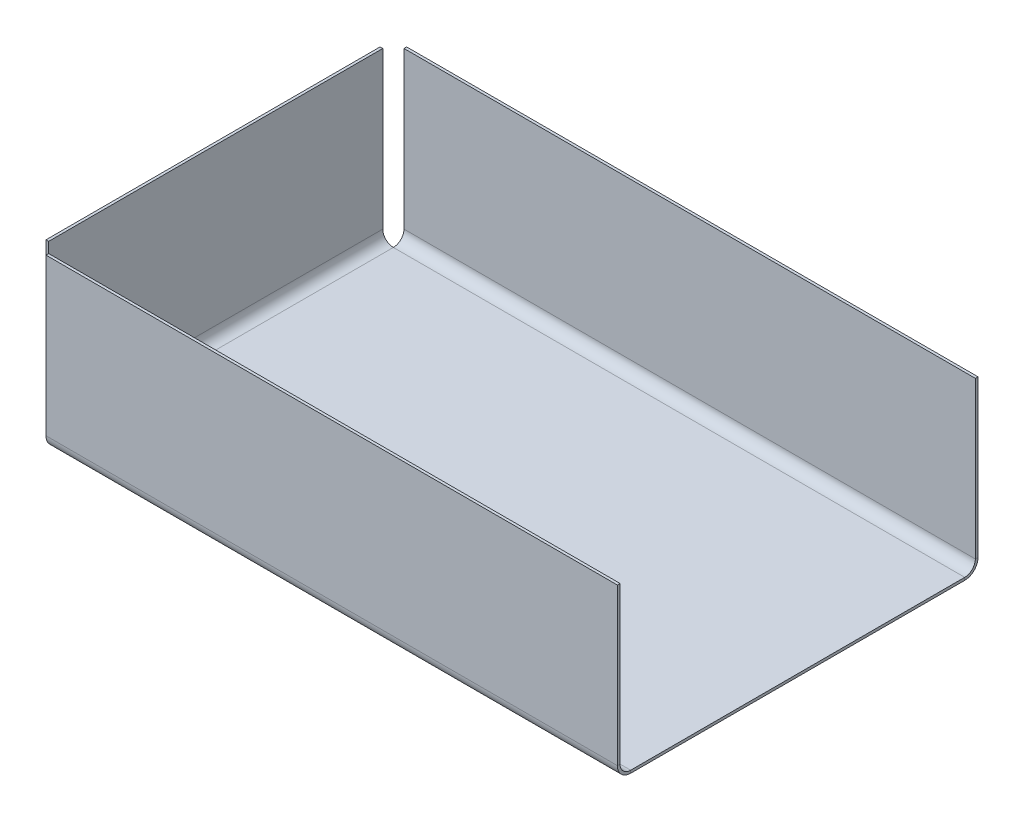
SolidWorks part; units mm, degrees
note: The reader was unsure of these and kept them because the rebuilt part matched: flange length of "Edge-Flange4", "Edge-Flange5".
ref_plane "Front Plane" through (0, 0, 0) normal (0, 0, 1) x (1, 0, 0)
ref_plane "Top Plane" through (0, 0, 0) normal (0, 1, 0) x (1, 0, 0)
ref_plane "Right Plane" through (0, 0, 0) normal (1, 0, 0) x (0, 0, -1)
sketch "Sketch1" plane through (0, 0, 0) normal (0, 1, 0) x (1, 0, 0)
  line L1 (-175, 100) -> (175, 100)
  line L2 (-175, 100) -> (-175, -100)
  line L3 (-175, -100) -> (175, -100)
  line L4 (175, 100) -> (175, -100)
  line L5 (-175, 100) -> (175, -100) construction
  line L6 (-175, -100) -> (175, 100) construction
  point P0 (0, 0)
  dimension "Length" = 350
  dimension "Width" = 200
base flange "Base-Flange1" sketch "Sketch1" thickness 1.6002 reverse thickness direction no parameters "D1"=6.35
edge flange "Edge-Flange4" sketch "Sketch24" flange angle 90 flange length 101.6002 flange position material inside bend radius 6.35 thickness 1.6002 parameters "D6"=10
sketch "Sketch24" plane through (-175, 0, 0) normal (1, 0, 0) x (0, 0, -1)
  line L2 (-100, 0) -> (-100, 100)
  line L3 (-100, 100) -> (100, 100)
  line L4 (100, 100) -> (100, 0)
  line L5 (100, 0) -> (-100, 0) construction
  line L6 (100, 0) -> (-100, 0)
  dimension "Height" = 100
bend "EdgeBend5" bend radius 6.35 bend angle 90 parameters "D5"=1
edge flange "Edge-Flange5" sketch "Sketch27" flange profiles "Sketch27", "Sketch29" flange angle 90 flange length 101.6002 flange position bend outside bend radius 6.35 thickness 1.6002 parameters "D6"=10, "D8"=1
sketch "Sketch27" plane through (0, 0, 100) normal (0, 0, -1) x (-1, 0, 0)
  line L2 (-175, 0) -> (-175, 100)
  line L3 (-175, 100) -> (167.0498, 100)
  line L4 (167.0498, 100) -> (167.0498, 0)
  line L5 (167.0498, 0) -> (-175, 0) construction
  line L6 (167.0498, 0) -> (-175, 0)
  dimension "D1" = 100
sketch "Sketch29" plane through (0, 0, -100) normal (0, 0, 1) x (1, 0, 0)
  line L0 (175, 0) -> (-167.0498, 0) construction
  line L1 (175, 0) -> (-167.0498, 0)
  line L2 (175, 0) -> (175, 100)
  line L3 (175, 100) -> (-167.0498, 100)
  line L4 (-167.0498, 100) -> (-167.0498, 0)
  dimension "D1" = 100
bend "EdgeBend6" bend radius 6.35 bend angle 90 parameters "D5"=2
bend "EdgeBend7" bend radius 6.35 bend angle 90 parameters "D5"=4
sketch "Bend-Lines1" [suppressed] plane through (0, 0, 0) normal (0, 1, 0) x (1, 0, 0)
sketch "Bounding-Box1" [suppressed] plane through (0, 0, 0) normal (0, 1, 0) x (1, 0, 0)
sheet metal parameters "Sheet-Metal2" thickness 1.6002 parameters "D1"=6.35
flat pattern "Flat-Pattern2" [suppressed]
sketch "Bend-Lines2" plane through (0, 0, 0) normal (0, 1, 0) x (1, 0, 0)
sketch3d "Bounding-Box2" [suppressed]
  line L0 (175, -100, 0) -> (-175, -100, 0) construction
  line L1 (175, 100, 0) -> (-175, 100, 0) construction
  line L2 (175, -100, 0) -> (175, 100, 0) construction
  line L3 (-175, -100, 0) -> (-175, 100, 0) construction
sheet metal parameters "Sheet-Metal6" thickness 1.6002 parameters "D1"=6.35
flat pattern "Flat-Pattern2"
sketch "Bend-Lines2" plane through (0, 0, 0) normal (0, 1, 0) x (1, 0, 0)
sketch3d "Bounding-Box2" [suppressed]
  line L0 (175, -100, 0) -> (-175, -100, 0) construction
  line L1 (175, 100, 0) -> (-175, 100, 0) construction
  line L2 (175, -100, 0) -> (175, 100, 0) construction
  line L3 (-175, -100, 0) -> (-175, 100, 0) construction
bend of the flat pattern "Flatten-<EdgeBend5>1"
sheet metal parameters "Sheet-Metal7" thickness 1.6002 parameters "D1"=6.35
flat pattern "Flat-Pattern2"
sketch "Bend-Lines2" plane through (0, 0, 0) normal (0, 1, 0) x (1, 0, 0)
  line L0 (175, 102.5) -> (-167.0498, 102.5) construction
  line L1 (-167.0498, -102.5) -> (175, -102.5) construction
  line L2 (-169.5498, 100) -> (-169.5498, -100) construction
  line L3 (175, 102.5) -> (-167.0498, 102.5) construction
  line L4 (-167.0498, -102.5) -> (175, -102.5) construction
  line L5 (-169.5498, 100) -> (-169.5498, -100) construction
sketch3d "Bounding-Box2" [suppressed]
  line L0 (175, -198.65, 0) -> (-265.6998, -198.65, 0) construction
  line L1 (175, 198.65, 0) -> (-265.6998, 198.65, 0) construction
  line L2 (175, -198.65, 0) -> (175, 198.65, 0) construction
  line L3 (-265.6998, -198.65, 0) -> (-265.6998, 198.65, 0) construction
bend of the flat pattern "Flatten-<EdgeBend5>1"
bend of the flat pattern "Flatten-<EdgeBend6>1"
bend of the flat pattern "Flatten-<EdgeBend7>1"
equation "\"Height\"= 100mm"
equation "\"D1@Sketch29\"=\"Height\""
equation "\"D1@Sketch27\"=\"Height\""
equation "\"Height@Sketch24\"=\"Height\""
